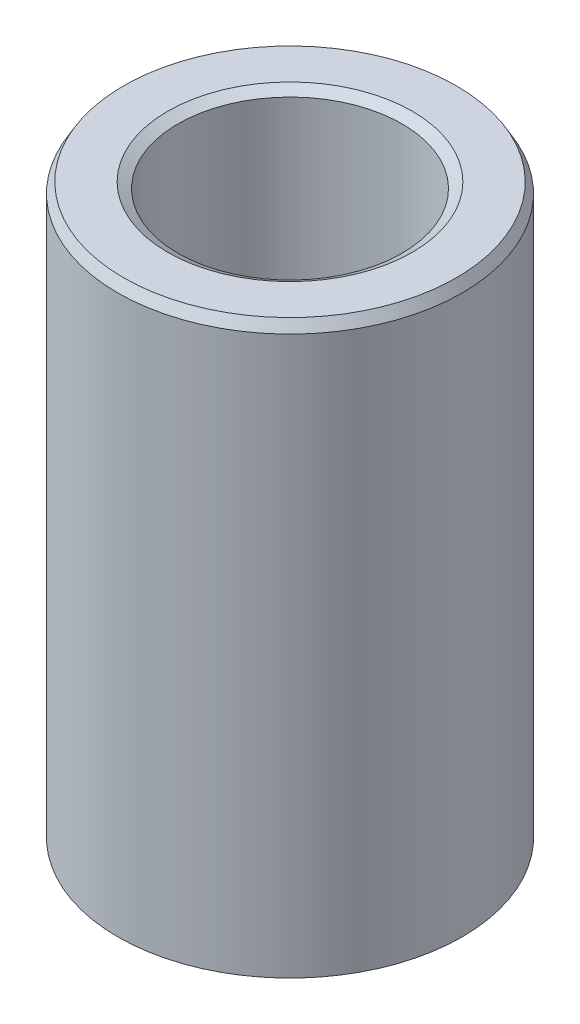
SolidWorks part; units mm, degrees
ref_plane "Front Plane" through (0, 0, 0) normal (0, 0, 1) x (1, 0, 0)
ref_plane "Top Plane" through (0, 0, 0) normal (0, 1, 0) x (1, 0, 0)
ref_plane "Right Plane" through (0, 0, 0) normal (1, 0, 0) x (0, 0, -1)
sketch "Sketch1" plane through (0, 0, 0) normal (0, 1, 0) x (1, 0, 0)
  circle A0 centre (0, 0) radius 40
  dimension "SLEEVE_OD" = 80
extrude "Boss-Extrude1" add sketch "Sketch1" along normal blind 133.2777
sketch "Sketch2" plane through (0, 0, 0) normal (0, 1, 0) x (1, 0, 0)
  circle A0 centre (0, 0) radius 26.0392
  dimension "BORE_D" = 52.0785
extrude "Cut-Extrude1" cut sketch "Sketch2" along normal through all
chamfer "Chamfer1" distance 2.3619 angle 30 4 edges at (0, 133.2777, 26.0392) (0, 0, 26.0392) (0, 0, 40) (0, 133.2777, 40) first distance on face at (0, 133.2777, 26.0392) first distance on face at (0, 0, 26.0392) first distance on face at (0, 133.2777, 40)
